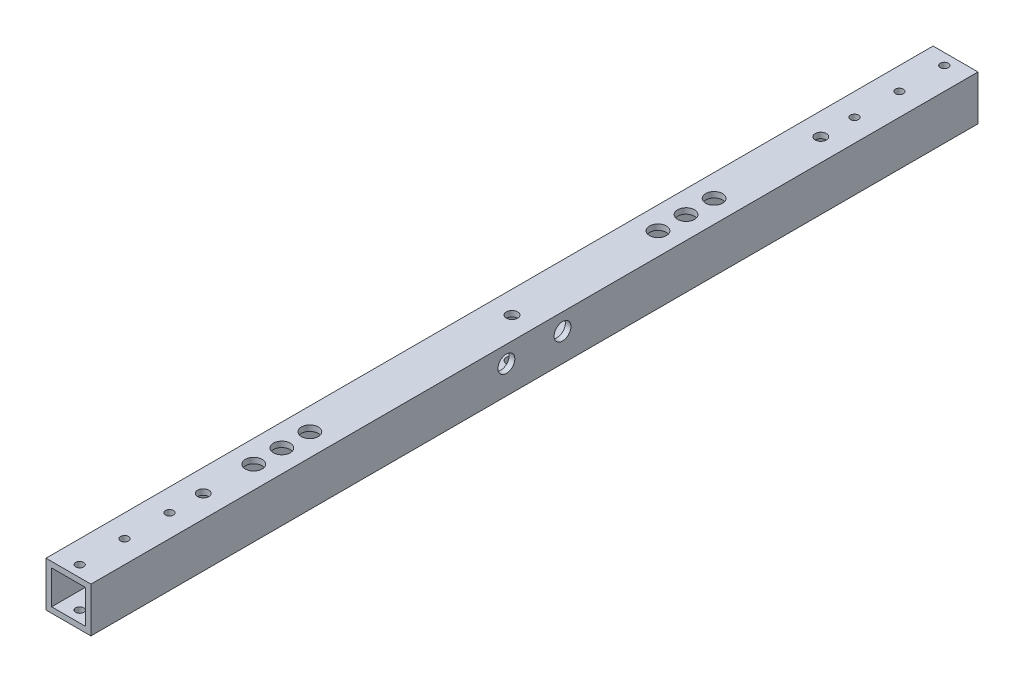
SolidWorks part; units mm, degrees
material "6061-T6 (SS)"
ref_plane "Front Plane" through (0, 0, 0) normal (0, 0, 1) x (1, 0, 0)
ref_plane "Top Plane" through (0, 0, 0) normal (0, 1, 0) x (1, 0, 0)
ref_plane "Right Plane" through (0, 0, 0) normal (1, 0, 0) x (0, 0, -1)
sketch "Sketch1" plane through (0, 0, 0) normal (0, 0, 1) x (1, 0, 0)
  line L1 (-12.7, -12.7) -> (12.7, -12.7)
  line L2 (-12.7, -12.7) -> (-12.7, 12.7)
  line L3 (-12.7, 12.7) -> (12.7, 12.7)
  line L4 (12.7, -12.7) -> (12.7, 12.7)
  line L5 (-12.7, -12.7) -> (12.7, 12.7) construction
  line L6 (-12.7, 12.7) -> (12.7, -12.7) construction
  point P0 (0, 0)
  dimension "D1" = 25.4
  dimension "D2" = 25.4
extrude "Extrude-Thin1" add sketch "Sketch1" along normal blind 501.65 thin thin type one direction reverse wall 3.175
hole_wizard "#8 Clearance Hole1" positions "3DSketch1" profile "Sketch3" hole size "#8" standard "ANSI Inch" end condition through all
sketch3d "3DSketch1"
  line L1 (12.7, 12.7, 0) -> (-12.7, 12.7, 0) construction
  line L6 (0, 12.7, 501.65) -> (0, 12.7, 0) construction
  line L7 (12.7, 12.7, 501.65) -> (-12.7, 12.7, 501.65) construction
  point P57 (0, 12.7, 6.35)
  point P59 (0, 12.7, 31.75)
  point P61 (0, 12.7, 57.15)
  point P63 (0, 12.7, 469.9)
  point P65 (0, 12.7, 444.5)
  point P67 (0, 12.7, 495.3)
  dimension "D1" = 25.4
  dimension "D2" = 25.4
  dimension "D3" = 6.35
  dimension "D4" = 25.4
  dimension "D5" = 25.4
  dimension "D6" = 6.35
sketch "Sketch3" plane through (0, 12.7, 495.3) normal (1, 0, 0) x (0, 0, 1)
  line L0 (0, 0) -> (0, 25.4)
  line L1 (0, 25.4) -> (2.2479, 25.4)
  line L2 (2.2479, 25.4) -> (2.2479, 0)
  line L5 (2.2479, 0) -> (0, 0)
  line L11 (0, -6.35) -> (0, 107.95) construction
  dimension "Thru Hole Dia." = 4.4958
  dimension "Thru Hole Depth" = 25.4
hole_wizard "1/4 (0.25) Diameter Hole1" positions "Sketch10" profile "Sketch11" hole size "1/4" standard "ANSI Inch"
sketch "Sketch10" plane through (381, 12.7, 250.825) normal (0, 1, 0) x (1, 0, 0)
  line L0 (-381, 174.625) -> (-381, -174.625) construction
  line L2 (-381, 174.625) -> (-381, 250.825) construction
  line L5 (-381, -174.625) -> (-381, -250.825) construction
  point P0 (-381, 174.625)
  point P2 (-381, 0)
  point P4 (-381, -174.625)
sketch "Sketch11" plane through (0, 12.7, 76.2) normal (1, 0, 0) x (0, 0, 1)
  line L0 (0, 0) -> (0, 30.4827)
  line L1 (0, 30.4827) -> (3.175, 28.575)
  line L2 (3.175, 28.575) -> (3.175, 0)
  line L3 (3.175, 0) -> (0, 0)
  line L4 (0, 30.4827) -> (-3.175, 28.575) construction
  line L5 (0, -6.35) -> (0, 107.95) construction
  dimension "Hole Dia." = 6.35
  dimension "Hole Depth" = 28.575
  dimension "Drill Angle" = 118
hole_wizard "3/8 (0.375) Diameter Hole2" positions "Sketch14" profile "Sketch15" hole size "3/8" standard "ANSI Inch" end condition through all
sketch "Sketch14" plane through (381, 12.7, 250.825) normal (0, 1, 0) x (1, 0, 0)
  point P9 (-92.583, 346.075)
  point P12 (-35.433, 346.075)
  point P18 (35.814, 346.075)
  point P21 (92.964, 346.075)
  point P24 (-22.9616, -346.775)
  point P27 (50.0634, -346.775)
  point P30 (123.0884, -346.775)
  point P33 (-381, 114.3)
  point P36 (-381, 98.425)
  point P39 (-381, 82.55)
  point P42 (-381, -114.3)
  point P45 (-381, -130.175)
  point P48 (-381, -146.05)
sketch "Sketch15" plane through (288.417, 12.7, -95.25) normal (1, 0, 0) x (0, 0, 1)
  line L0 (0, 0) -> (0, 25.4)
  line L1 (0, 25.4) -> (4.7625, 25.4)
  line L2 (4.7625, 25.4) -> (4.7625, 0)
  line L3 (4.7625, 0) -> (0, 0)
  line L4 (0, -6.35) -> (0, 107.95) construction
  dimension "Thru Hole Dia." = 9.525
  dimension "Thru Hole Depth" = 25.4
hole_wizard "3/8 (0.375) Diameter Hole3" positions "Sketch16" profile "Sketch17" hole size "3/8" standard "ANSI Inch" end condition through all
sketch "Sketch16" plane through (12.7, -82.55, 250.825) normal (1, 0, 0) x (0, 0, -1)
  point P0 (-15.875, 85.725)
  point P3 (15.875, 85.725)
  point P6 (15.875, 53.975)
  point P9 (-15.875, 53.975)
sketch "Sketch17" plane through (12.7, 3.175, 266.7) normal (0, 1, 0) x (0, 0, -1)
  line L0 (0, 0) -> (0, 25.4)
  line L1 (0, 25.4) -> (4.7625, 25.4)
  line L2 (4.7625, 25.4) -> (4.7625, 0)
  line L3 (4.7625, 0) -> (0, 0)
  line L4 (0, -6.35) -> (0, 107.95) construction
  dimension "Thru Hole Dia." = 9.525
  dimension "Thru Hole Depth" = 25.4
